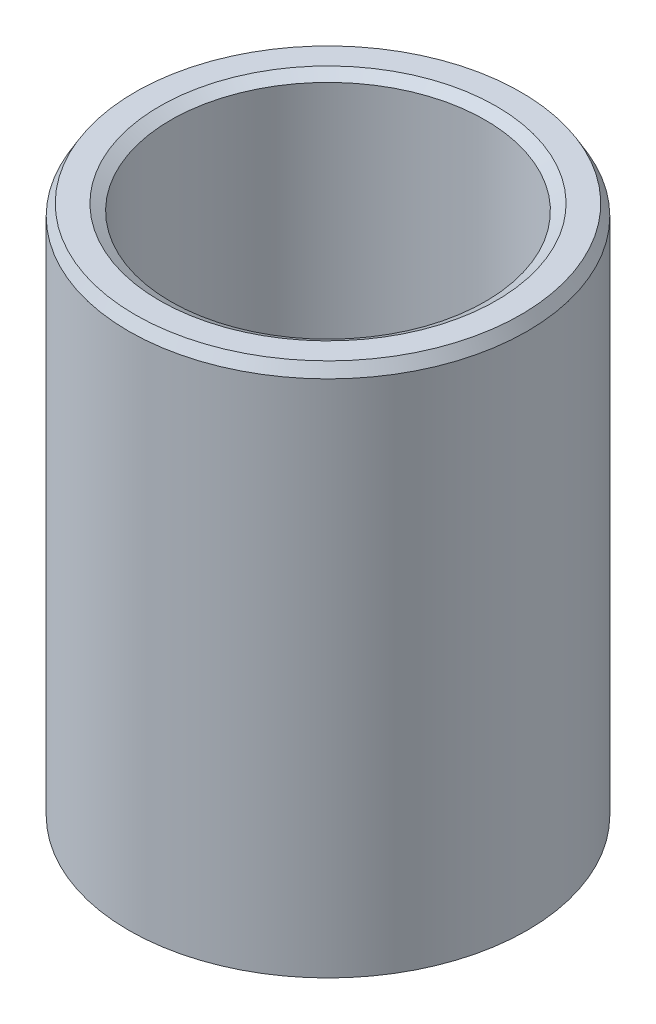
SolidWorks part; units mm, degrees
ref_plane "Front Plane" through (0, 0, 0) normal (0, 0, 1) x (1, 0, 0)
ref_plane "Top Plane" through (0, 0, 0) normal (0, 1, 0) x (1, 0, 0)
ref_plane "Right Plane" through (0, 0, 0) normal (1, 0, 0) x (0, 0, -1)
sketch "Sketch1" plane through (0, 0, 0) normal (0, 1, 0) x (1, 0, 0)
  circle A0 centre (0, 0) radius 47.5
  dimension "SLEEVE_OD" = 95
extrude "Boss-Extrude1" add sketch "Sketch1" along normal blind 127.8362
sketch "Sketch2" plane through (0, 0, 0) normal (0, 1, 0) x (1, 0, 0)
  circle A0 centre (0, 0) radius 37.4902
  dimension "BORE_D" = 74.9805
extrude "Cut-Extrude1" cut sketch "Sketch2" along normal through all
chamfer "Chamfer1" distance 2.6416 angle 30 4 edges at (0, 127.8362, 37.4902) (0, 0, 37.4902) (0, 0, 47.5) (0, 127.8362, 47.5) first distance on face at (0, 127.8362, 37.4902) first distance on face at (0, 0, 37.4902) first distance on face at (0, 127.8362, 47.5)
